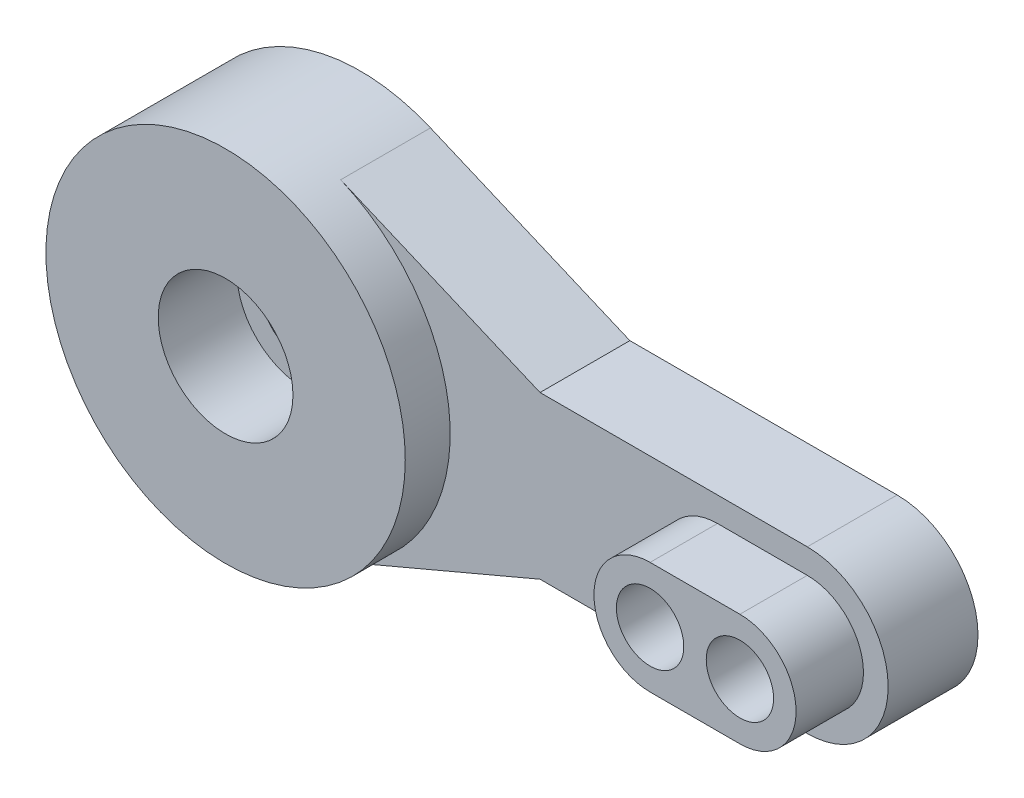
SolidWorks part; units mm, degrees
ref_plane "Top Plane" through (0, 0, 0) normal (0, 0, 1) x (1, 0, 0)
ref_plane "Right Plane" through (0, 0, 0) normal (0, 1, 0) x (1, 0, 0)
ref_plane "Front Plane" through (0, 0, 0) normal (1, 0, 0) x (0, 0, -1)
sketch "Sketch1" plane through (0, 0, 0) normal (0, 0, 1) x (1, 0, 0)
  line L0 (0, 0) -> (23.9, 0) construction
  line L1 (3.1239, 7.3649) -> (12, 3.6)
  line L2 (12, 3.6) -> (23.9, 3.6)
  line L3 (12, -3.6) -> (23.9, -3.6)
  line L4 (3.1239, -7.3649) -> (12, -3.6)
  circle A0 centre (0, 0) radius 3 construction
  circle A1 centre (23.9, 0) radius 1.5 construction
  circle A2 centre (19.9, 0) radius 1.5 construction
  arc A3 (3.1239, 7.3649) -> (3.1239, -7.3649) centre (0, 0) ccw
  arc A4 (23.9, -3.6) -> (23.9, 3.6) centre (23.9, 0) ccw
  point P17 (-8, 0)
  point P18 (27.5, 0)
  dimension "D1" = 23.9
  dimension "D2" = 3
  dimension "D3" = 3
  dimension "D5" = 6
  dimension "D6" = 16
  dimension "D7" = 35.5
  dimension "D4" = 19.9
  dimension "D8" = 12
extrude "Boss-Extrude1" add sketch "Sketch1" along normal blind 4
sketch "Sketch4" plane through (0, 0, 4) normal (0, 0, 1) x (1, 0, 0)
  circle A0 centre (0, 0) radius 8
  arc A1 (3.1239, 7.3649) -> (3.1239, -7.3649) centre (0, 0) ccw construction
extrude "Boss-Extrude2" add sketch "Sketch4" along normal blind 2
sketch "Sketch5" plane through (0, 0, 4) normal (0, 0, 1) x (1, 0, 0)
  line L0 (23.9, 0) -> (19.9, 0) construction
  line L1 (0, 0) -> (23.9, 0) construction
  line L2 (23.9, -2.5) -> (19.9, -2.5)
  line L3 (23.9, 2.5) -> (19.9, 2.5)
  arc A0 (23.9, -2.5) -> (23.9, 2.5) centre (23.9, 0) ccw
  arc A1 (19.9, 2.5) -> (19.9, -2.5) centre (19.9, 0) ccw
  point P5 (21.9, 0)
  dimension "D1" = 5
extrude "Boss-Extrude3" add sketch "Sketch5" along normal blind 3
hole_wizard "Ø3.0 (3) Diameter Hole1" positions "Sketch8" profile "Sketch9" hole size "Ø3.0" standard "ISO" end condition through all
sketch "Sketch8" plane through (0, 0, 0) normal (0, 0, -1) x (-1, 0, 0)
  point P0 (-23.9, 0)
  point P3 (-19.9, 0)
sketch "Sketch9" plane through (23.9, 0, 0) normal (1, 0, 0) x (0, 1, 0)
  line L0 (0, 0) -> (0, 7)
  line L1 (0, 7) -> (1.5, 7)
  line L2 (1.5, 7) -> (1.5, 0)
  line L5 (1.5, 0) -> (0, 0)
  line L11 (0, -6.35) -> (0, 107.95) construction
  dimension "Thru Hole Dia." = 3
  dimension "Thru Hole Depth" = 7
hole_wizard "Ø6.0 (6) Diameter Hole1" positions "Sketch10" profile "Sketch11" hole size "Ø6.0" standard "ISO" end condition through all
sketch "Sketch10" plane through (0, 0, 0) normal (0, 0, -1) x (-1, 0, 0)
  point P0 (0, 0)
sketch "Sketch11" plane through (0, 0, 0) normal (1, 0, 0) x (0, 1, 0)
  line L0 (0, 0) -> (0, 7)
  line L1 (0, 7) -> (3, 7)
  line L2 (3, 7) -> (3, 0)
  line L5 (3, 0) -> (0, 0)
  line L11 (0, -6.35) -> (0, 107.95) construction
  dimension "Thru Hole Dia." = 6
  dimension "Thru Hole Depth" = 7
sketch "Sketch12" plane through (0, 0, 0) normal (0, 0, 1) x (1, 0, 0)
  circle A0 centre (0, 0) radius 2
  circle A1 centre (0, 0) radius 3 construction
  circle A2 centre (0, 0) radius 3
  dimension "D1" = 1
extrude "Boss-Extrude4" add sketch "Sketch12" along normal offset from surface (2.5 mm away) 3.5 up to face at (3, 0, 6)
